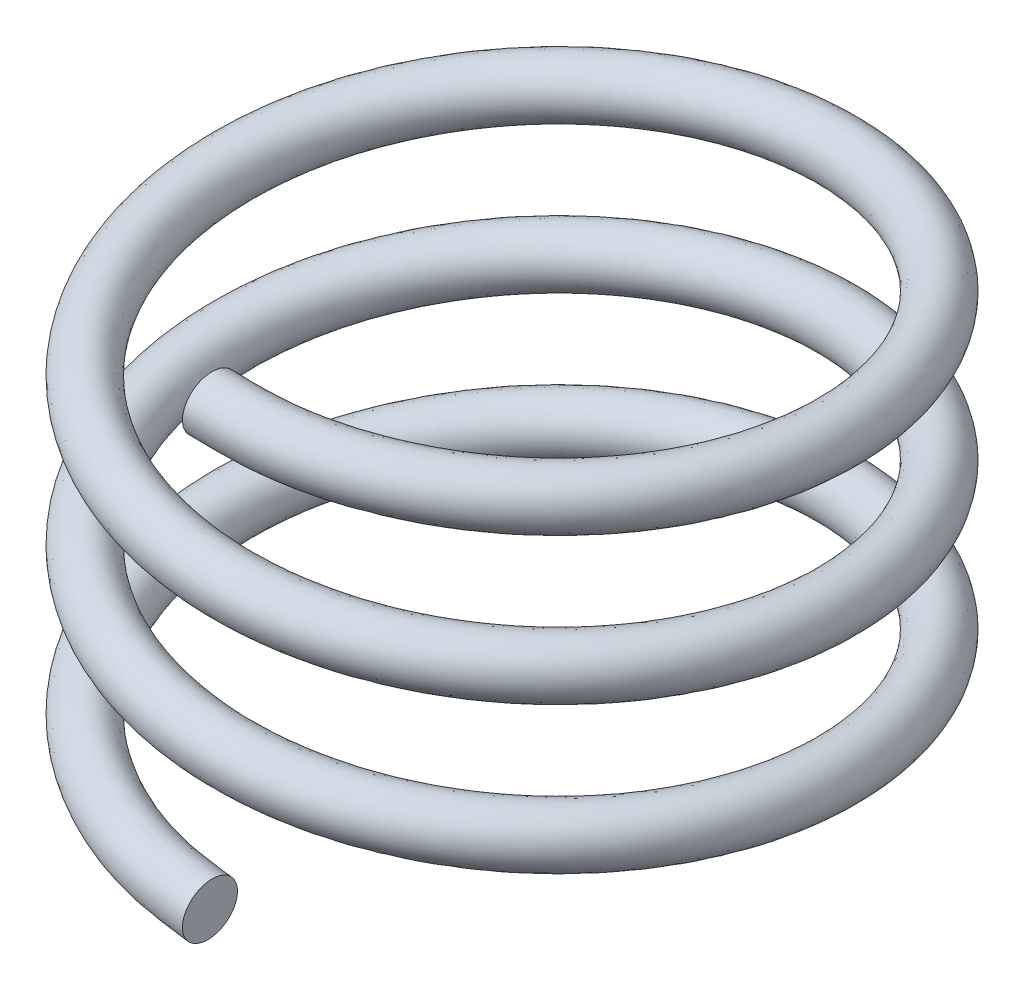
SolidWorks part; units mm, degrees
note: '?' marks a value the reader was unsure of.
ref_plane "Plane1" through (0, 0, 0) normal (0, 0, 1) x (1, 0, 0)
ref_plane "Plane2" through (0, 0, 0) normal (0, 1, 0) x (1, 0, 0)
ref_plane "Plane3" through (0, 0, 0) normal (1, 0, 0) x (0, 0, -1)
sketch "Sketch1" plane through (0, 0, 0) normal (0, 1, 0) x (1, 0, 0)
  circle A0 centre (0, 0) radius 6.985
  dimension "D1" = 13.97
curve "Helix1" pitch 3.3867 height 10.16 turns 3
ref_plane "Plane4" through (0, 0, 6.985) normal (-0.997, 0.0769, 0) x (0, 0, 1)
sketch "Sketch2" plane through (0, 0, 6.985) normal (-0.997, 0.0769, 0) x (0, 0, 1)
  circle A0 centre (0.0002, -0.0006) radius 0.635
  dimension "D1" = 1.27
sweep "Base-Sweep" add profiles "Sketch2" path "Helix1"
ref_axis "Axis1" through (0, 50, 0) along (0, -1, 0)?
